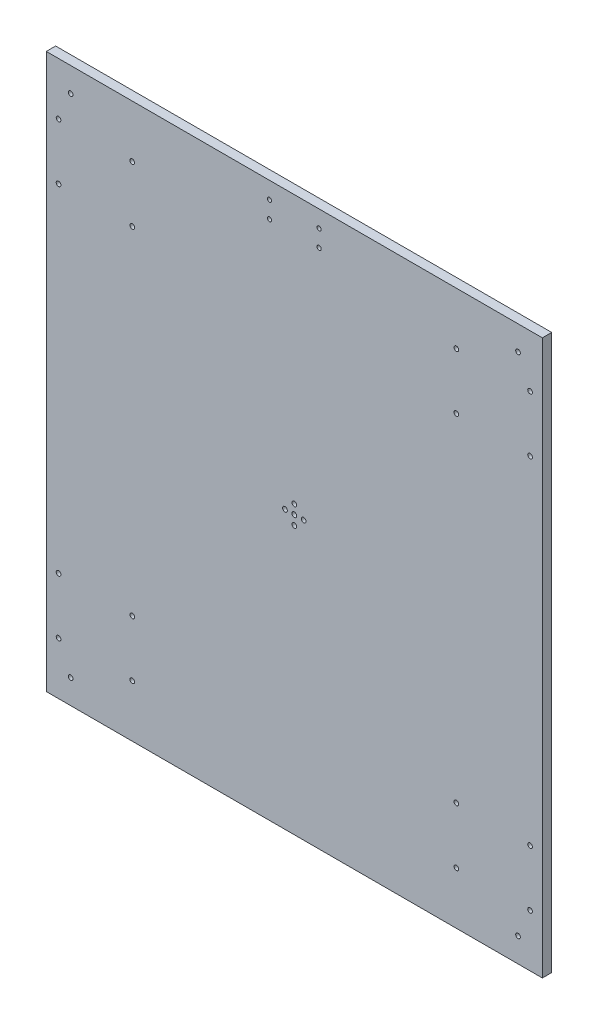
SolidWorks part; units mm, degrees
ref_plane "Спереди" through (0, 0, 0) normal (0, 0, 1) x (1, 0, 0)
ref_plane "Сверху" through (0, 0, 0) normal (0, 1, 0) x (1, 0, 0)
ref_plane "Справа" through (0, 0, 0) normal (1, 0, 0) x (0, 0, -1)
sketch "Эскиз3" plane through (0, 0, 0) normal (0, 0, 1) x (1, 0, 0)
  line L0 (0, 0) -> (0, 10) construction
  line L5 (265, -296.15) -> (-265, -296.15)
  line L6 (265, -296.15) -> (265, 296.15)
  line L7 (265, 296.15) -> (-265, 296.15)
  line L8 (-265, -296.15) -> (-265, 296.15)
  line L9 (0, 0) -> (10, 0) construction
  line L10 (0, 0) -> (0, -10) construction
  line L11 (0, 0) -> (-10, 0) construction
  circle A0 centre (0, 0) radius 2.55
  circle A1 centre (0, 10) radius 2.55
  circle A2 centre (10, 0) radius 2.55
  circle A3 centre (0, -10) radius 2.55
  circle A4 centre (-10, 0) radius 2.55
  point P0 (0, 0)
  point P5 (-265, 0)
  point P6 (0, 296.15)
  point P21 (0, 0)
  dimension "D3" = 5.1
  dimension "D4" = 5.1
  dimension "D1" = 592.3
  dimension "D2" = 530
  dimension "D5" = 10
  dimension "D6" = 4
extrude "Бобышка-Вытянуть1" add sketch "Эскиз3" along normal blind 10
sketch "Эскиз4" plane through (0, 0, 10) normal (0, 0, 1) x (1, 0, 0)
  line L0 (265, 296.15) -> (-265, 296.15) construction
  line L1 (-265, 296.15) -> (-265, -296.15) construction
  circle A0 centre (-239, 270.15) radius 2.5
  dimension "D1" = 5
  dimension "D2" = 26
  dimension "D3" = 26
extrude "Вырез-Вытянуть1" cut sketch "Эскиз4" against normal through all contours A0
pattern_linear "Линейный массив1" count 2 spacing 478 along (1, 0, 0) count 2 spacing 540.3 along (0, -1, 0) of "Вырез-Вытянуть1"
sketch "Эскиз7" plane through (0, 0, 0) normal (0, 0, -1) x (-1, 0, 0)
  line L9 (-26.5, 278.15) -> (26.5, 278.15) construction
  line L10 (-26.5, 278.15) -> (-26.5, 260.15) construction
  line L11 (-26.5, 260.15) -> (26.5, 260.15) construction
  line L16 (26.5, 278.15) -> (26.5, 260.15) construction
  line L17 (-265, 296.15) -> (265, 296.15) construction
  circle A0 centre (-26.5, 278.15) radius 2.25
  circle A1 centre (26.5, 278.15) radius 2.25
  circle A2 centre (-26.5, 260.15) radius 2.25
  circle A3 centre (26.5, 260.15) radius 2.25
  point P4 (0, 260.15)
  dimension "D4" = 4.5
  dimension "D5" = 4.5
  dimension "D6" = 4.5
  dimension "D7" = 4.5
  dimension "D1" = 53
  dimension "D2" = 18
  dimension "D3" = 18
extrude "Вырез-Вытянуть2" cut sketch "Эскиз7" against normal through all
sketch "Эскиз8" plane through (0, 0, 0) normal (0, 0, -1) x (-1, 0, 0)
  line L0 (160, 170.15) -> (265, 250.15) construction
  line L1 (265, 250.15) -> (160, 250.15) construction
  line L2 (265, 250.15) -> (265, 170.15) construction
  line L3 (265, 170.15) -> (160, 170.15) construction
  line L4 (160, 250.15) -> (160, 170.15) construction
  line L5 (160, 250.15) -> (265, 170.15) construction
  line L6 (265, 296.15) -> (265, -296.15) construction
  line L7 (-265, 296.15) -> (265, 296.15) construction
  circle A0 centre (173.125, 180.15) radius 2.5
  circle A1 centre (173.125, 240.15) radius 2.5
  circle A2 centre (251.875, 240.15) radius 2.5
  circle A3 centre (251.875, 180.15) radius 2.5
  point P4 (0, 0)
  point P14 (162.0842, 296.15)
  point P15 (178.125, 229.9595)
  point P16 (0, 0)
  point P17 (0, 0)
  point P18 (148.0057, 126.7066)
  point P23 (0, 0)
  dimension "D3" = 5
  dimension "D4" = 5
  dimension "D5" = 5
  dimension "D6" = 5
  dimension "D1" = 105
  dimension "D2" = 80
  dimension "D7" = 60
  dimension "D8" = 46
extrude "Вырез-Вытянуть3" cut sketch "Эскиз8" against normal through all
pattern_linear "Линейный массив2" count 2 spacing 420.3 along (0, -1, 0) count 2 spacing 424.995 along (1, 0, 0) of "Вырез-Вытянуть3"
equation "\"Ширина груза\"= 420"
equation "\"Глубина груза\"= 490"
equation "\"Высота груза\"= 297"
equation "\"Ширина ячейки\"= \"Ширина груза\" + 10"
equation "\"Глубина ячейки\"= \"Глубина груза\" + 10"
equation "\"Высота ячейки\"= \"Высота груза\" + 10 + 13"
equation "\"Колво ячеек ширина\"= 2"
equation "\"Колво ячеек высота\"= 2"
equation "\"Толщина стенки\"= 10"
equation "\"Крепление дверцы\"= 5"
equation "\"Ширина рейки\"= \"Толщина шестерни\""
equation "\"Высота рейки\"= 20"
equation "\"Высота пола\"= 20"
equation "\"Колво полозьев\"= 5"
equation "\"Отступ рейки\"= 20"
equation "\"Глубина каретки\"= \"Глубина ячейки\" + 30 + \"Мотор Y высота корпуса\" + 20"
equation "\"Длинна рейки\"= ( \"Ширина ячейки\" + \"Толщина стенки\" + \"Крепление дверцы\" ) * \"Колво ячеек ширина\" + \"Ширина ячейки выгрузки\" * \"Колво выгрузки\" + \"Толщина стенки\""
equation "\"Отступ шпильки\"= 26"
equation "\"Диаметр шпильки\"= 5"
equation "\"D1@Бобышка-Вытянуть1\" = \"Толщина стенки\""
equation "\"D1@Эскиз4\"= \"Диаметр шпильки\""
equation "\"D2@Эскиз4\"=\"Отступ шпильки\""
equation "\"D3@Эскиз4\"= \"Отступ шпильки\""
equation "\"D2@Эскиз3\"=\"Ширина ячейки\" + \"Ширина пластины\" * 2"
equation "\"D1@Эскиз3\"=\"Глубина каретки\" "
equation "\"D3@Линейный массив1\"=\"Ширина ячейки\"  +\"Ширина пластины\" *2 - \"Отступ шпильки\" * 2"
equation "\"D4@Линейный массив1\"=\"Глубина каретки\" + \"Ширина рейки\" * 2 - \"Отступ шпильки\" * 2 - \"Ширина рейки\" * 2"
equation "\"Длинна шпильки\"= ( \"Высота ячейки\" + \"Толщина стенки\" + \"Высота пола\" ) * \"Колво ячеек высота\" + ( \"Толщина стенки\" + \"Отступ рейки\" ) * 2 "
equation "\"Ширина пластины\"= 50  "
equation "\"Высота зона выгрузки\"= \"Высота ячейки\" * 2 + \"Толщина стенки\" * 2"
equation "\"Колво выгрузки\"= 1"
equation "\"Отступ крепления мотора фиксации\" = 30"
equation "\"Мотор X ширина корпуса\"= 42.3"
equation "\"Мотор X высота корпуса\"= 42.3"
equation "\"Мотор X длина корпуса\"= 40"
equation "\"Мотор X вылет вала\"= 19.8"
equation "\"Мотор Y ширина корпуса\"= 42.3"
equation "\"Мотор Y высота корпуса\"= 42.3"
equation "\"Мотор Y длина корпуса\"= 48"
equation "\"Мотор Y вылет вала\"= 30"
equation "\"Мотор Z ширина корпуса\"= 42"
equation "\"Мотор Z высота корпуса\"= 42"
equation "\"Мотор Z длина корпуса\"= 40"
equation "\"Мотор Z вылет вала\"= 23"
equation "\"Мотор диаметр вала ПРЕДВ\"= 5"
equation "\"Мотор шаг крепления ПРЕДВ\"= 31"
equation "\"Мотор диаметр отверстий ПРЕДВ\"= 3"
equation "\"Мотор глубина отверстий ПРЕДВ\"= 4.5"
equation "\"Мотор диаметр буртика ПРЕДВ\"= 22"
equation "\"Мотор высота буртика ПРЕДВ\"= 2"
equation "\"Мотор диаметр шкива ПРЕДВ\"= 16"
equation "\"Мотор длина шкива ПРЕДВ\"= 12"
equation "\"Мотор отступ шкива ПРЕДВ\"= 5"
equation "\"Мотор X шаг градусов\"= 1.8"
equation "\"Мотор Y шаг градусов\"= 1.8"
equation "\"Мотор Z шаг градусов\"= 1.8"
equation "\"Мотор Y диаметр ротора\"= 25.78"
equation "\"Толщина шестерни\"= 10"
equation "\"Ширина ячейки выгрузки\"= \"Ширина ячейки\" + \"Толщина стенки\" + \"Отступ крепления мотора фиксации\"*2"
